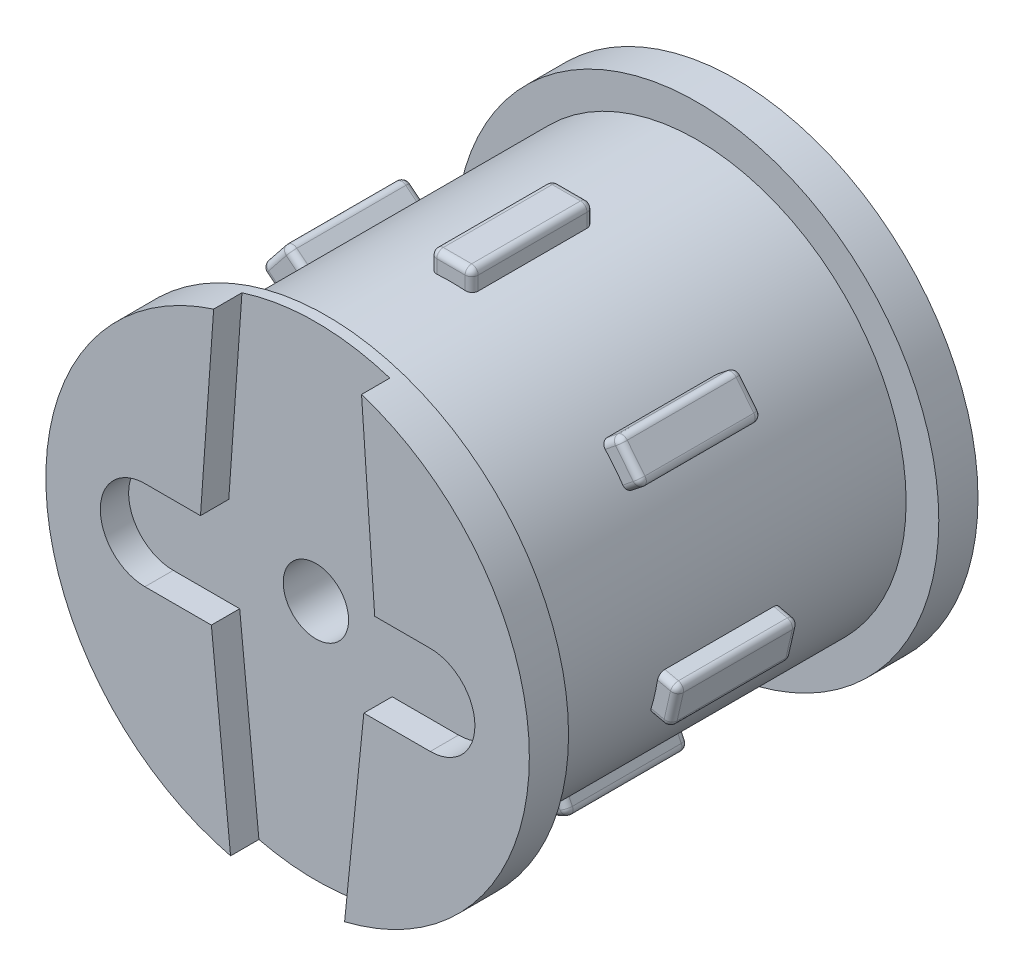
SolidWorks part; units mm, degrees
ref_plane "Ebene vorne" through (0, 0, 0) normal (0, 0, 1) x (1, 0, 0)
ref_plane "Ebene oben" through (0, 0, 0) normal (0, 1, 0) x (1, 0, 0)
ref_plane "Ebene rechts" through (0, 0, 0) normal (1, 0, 0) x (0, 0, -1)
sketch "Skizze1" plane through (0, 0, 0) normal (0, 0, 1) x (1, 0, 0)
  circle A0 centre (0, 0) radius 9.6
  dimension "D1" = 19.2
extrude "Aufsatz-Linear austragen1" add sketch "Skizze1" along normal blind 10.3 and the other way blind 10.3
ref_axis "Rotationsachse" through (0, 0, -10.3) along (0, 0, 1)
sketch "Skizze2" plane through (0, 0, 10.3) normal (0, 0, 1) x (1, 0, 0)
  circle A0 centre (0, 0) radius 11.1
  dimension "D1" = 22.2
extrude "Aufsatz-Linear austragen2" add sketch "Skizze2" against normal blind 1.8
sketch "Skizze3" plane through (0, 0, -10.3) normal (0, 0, -1) x (-1, 0, 0)
  circle A0 centre (0, 0) radius 11.1
  dimension "D1" = 22.2
extrude "Aufsatz-Linear austragen3" add sketch "Skizze3" against normal blind 1.8
sketch "Skizze12" plane through (0, 0, 10.3) normal (0, 0, 1) x (1, 0, 0)
  line L0 (1.9899, -17.001) -> (3.5, -2.05)
  line L1 (-3.05, 2.05) -> (3.05, 2.05)
  line L2 (-3.05, 2.05) -> (-3.05, -2.05)
  line L3 (-3.05, -2.05) -> (3.05, -2.05)
  line L4 (3.05, 2.05) -> (3.05, -2.05)
  line L5 (-3.05, 2.05) -> (3.05, -2.05) construction
  line L6 (-3.05, -2.05) -> (3.05, 2.05) construction
  line L7 (3.05, 2.05) -> (6.55, 2.05)
  line L8 (3.05, 2.05) -> (3.05, -2.05)
  line L9 (3.05, -2.05) -> (6.55, -2.05)
  line L10 (6.55, 2.05) -> (6.55, -2.05)
  line L11 (-3.05, -2.05) -> (-3.5, -2.05)
  line L12 (-1.9899, -17.001) -> (-3.5, -2.05)
  line L13 (4, 2.05) -> (2.7431, 19.7448)
  line L14 (-4, 2.05) -> (-2.7431, 19.7448)
  line L16 (-3.05, -2.05) -> (-6.55, -2.05)
  line L17 (-3.05, -2.05) -> (-3.05, 2.05)
  line L18 (-3.05, 2.05) -> (-6.55, 2.05)
  line L19 (-6.55, -2.05) -> (-6.55, 2.05)
  circle A0 centre (6.55, 0) radius 2.05
  circle A1 centre (0, -16.8) radius 2
  circle A2 centre (0, 19.55) radius 2.75
  circle A3 centre (-6.55, 0) radius 2.05
  point P0 (0, 0)
  point P12 (0, -2.05)
  circle M11 centre (0, 0) radius 11.1
  dimension "D5" = 4
  dimension "D9" = 17.5
  dimension "D13" = 5.5
  dimension "D6" = 4.1
  dimension "D2" = 4.1
  dimension "D1" = 6.1
  dimension "D3" = 3.5
  dimension "D4" = 14.75
  dimension "D7" = 3.5
  dimension "D8" = 3.5
  dimension "D10" = 4
  dimension "D11" = 4
  dimension "D12" = 3.5
extrude "Schnitt-Linear austragen1" cut sketch "Skizze12" against normal blind 1.3 contours A1 M11 | L11 L9 L3 M11 | L4 L1 L2 L3 | A0 L7 L4 L9 | L10 A0 | L10 A0 | L18 L1 L7 L13 L14 M11 | A2 L14 L13 M11 | L17 L16 L19 L18 | A3 | A2 | L2 L1 L4 L3 region at (0, -13.1061, 10.3) region at (0, -6.3029, 10.3) region at (4.0504, 0, 10.3) region at (0, 0, 10.3) region at (5.68, 0, 10.3) region at (7.42, 0, 10.3) region at (0, 6.3626, 10.3) region at (0, 14.1384, 10.3)
sketch "Skizze8" plane through (0, 0, 0) normal (1, 0, 0) x (0, 0, -1)
  line L0 (10.3, 0) -> (10.3, 8)
  line L1 (10.3, -11.1) -> (10.3, 11.1) construction
  line L2 (10.3, 8) -> (8.5, 8)
  line L3 (8.5, 11.1) -> (8.5, -11.1) construction
  line L4 (8.5, 8) -> (-6.7, 3.5)
  line L6 (-6.7, 3.5) -> (-6.7, 0)
  line L7 (-6.7, 0) -> (10.3, 0)
  dimension "D1" = 8
  dimension "D2" = 3.5
  dimension "D3" = 17
revolve "Schnitt-Rotation1" cut sketch "Skizze8" angle 360 about axis through (0, 0, -10.3) along (0, 0, 1)
ref_plane "Schnittebene_Zaehne" through (0, 0, 0) normal (0, 0, -1) x (-1, 0, 0)
sketch "Skizze11" plane through (0, 0, 0) normal (0, 0, -1) x (-1, 0, 0)
  line L0 (0, 0) -> (0, 12.664) construction
  line L6 (-0.95, 8.71) -> (0.95, 8.71)
  line L7 (-0.95, 8.71) -> (-0.95, 10.49)
  line L8 (-0.95, 10.49) -> (0.95, 10.49)
  line L9 (0.95, 8.71) -> (0.95, 10.49)
  line L10 (-0.95, 8.71) -> (0.95, 10.49) construction
  line L11 (-0.95, 10.49) -> (0.95, 8.71) construction
  circle A1 centre (0, 0) radius 9.6 construction
  point P3 (0, 9.6)
  dimension "D1" = 0.89
  dimension "D2" = 1.9
extrude "Aufsatz-Linear austragen4" add sketch "Skizze11" along normal blind 2.8 and the other way blind 2.8
pattern_circular "Kreismuster2" count 7 over 360 about axis through (0, 0, -10.3) along (0, 0, 1) of "Aufsatz-Linear austragen4"
fillet "Verrundung1" radius 0.3 56 edges at (8.2014, 6.5404, 2.8) (7.6091, 7.2831, 0) (8.2014, 6.5404, -2.8) (8.7937, 5.7977, 0) (-8.4274, 5.5055, 2.8) (-7.2428, 6.991, 2.8) (-7.2428, 6.991, -2.8) (-8.4274, 5.5055, -2.8) (-9.5588, -3.1562, -2.8) (-9.9816, -1.3038, -2.8) (-9.5588, -3.1562, 2.8) (-9.9816, -1.3038, 2.8) (-5.2041, -8.6168, -2.8) (-3.4922, -9.4412, -2.8) (-3.4922, -9.4412, 2.8) (-5.2041, -8.6168, 2.8) (5.2041, -8.6168, 2.8) (3.4922, -9.4412, 2.8) (3.4922, -9.4412, -2.8) (5.2041, -8.6168, -2.8) (9.5588, -3.1562, 2.8) (9.5588, -3.1562, -2.8) (9.9816, -1.3038, 2.8) (9.9816, -1.3038, -2.8) (8.4274, 5.5055, 2.8) (8.4274, 5.5055, -2.8) (7.2428, 6.991, -2.8) (7.2428, 6.991, 2.8) (0.95, 10.0214, 2.8) (0.95, 10.0214, -2.8) (-0.95, 10.0214, -2.8) (-0.95, 10.0214, 2.8) (10.4384, -1.4081, 0) (10.227, -2.3342, 2.8) (10.227, -2.3342, -2.8) (10.0156, -3.2604, 0) (4.5514, -9.4512, 2.8) (4.5514, -9.4512, -2.8) (5.4074, -9.039, 0) (3.6955, -9.8634, 0) (-4.5514, -9.4512, 2.8) (-4.5514, -9.4512, -2.8) (-5.4074, -9.039, 0) (-3.6955, -9.8634, 0) (-10.227, -2.3342, 2.8) (-10.227, -2.3342, -2.8) (-10.0156, -3.2604, 0) (-10.4384, -1.4081, 0) (-8.2014, 6.5404, -2.8) (-8.2014, 6.5404, 2.8) (-8.7937, 5.7977, 0) (-7.6091, 7.2831, 0) (0, 10.49, -2.8) (0, 10.49, 2.8) (0.95, 10.49, 0) (-0.95, 10.49, 0)
sketch "Skizze14" plane through (0, 0, 10.3) normal (0, 0, 1) x (1, 0, 0)
  circle A0 centre (0, 0) radius 1.5
  dimension "D1" = 3
extrude "Schnitt-Linear austragen2" cut sketch "Skizze14" against normal up to surface (3.6 mm away) up to face at (-3.5, 0, 6.7)
